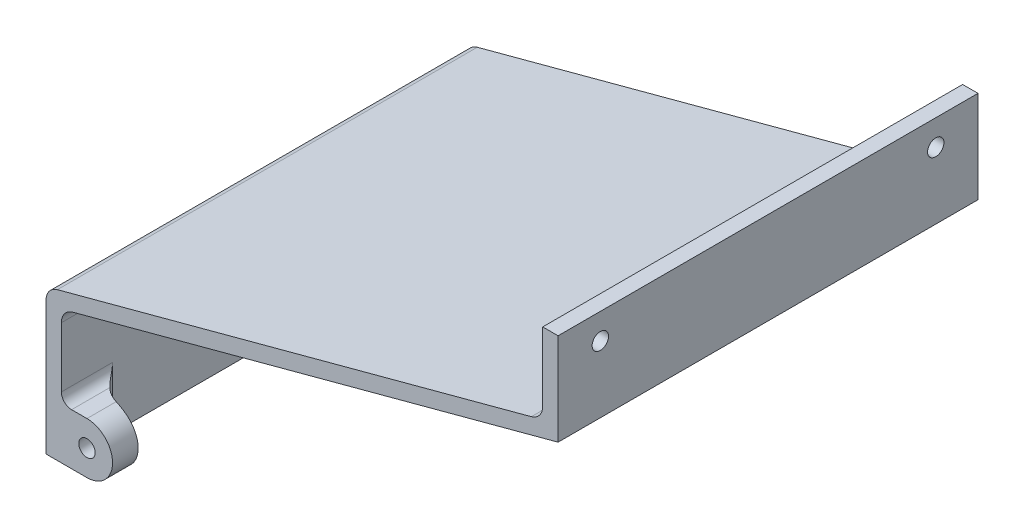
SolidWorks part; units mm, degrees
material "ABS"
ref_plane "前视基准面" through (0, 0, 0) normal (0, 0, 1) x (1, 0, 0)
ref_plane "上视基准面" through (0, 0, 0) normal (0, 1, 0) x (1, 0, 0)
ref_plane "右视基准面" through (0, 0, 0) normal (1, 0, 0) x (0, 0, -1)
sketch "草图1" plane through (0, 0, 0) normal (0, 0, 1) x (1, 0, 0)
  line L0 (49.6812, 34.5218) -> (49.6812, 16.5218)
  line L1 (49.6812, 16.5218) -> (-47.3188, -9.4692)
  line L2 (49.6812, 34.5218) -> (46.6812, 34.5218)
  line L3 (-47.3188, -9.4692) -> (-47.3188, -35.4782)
  line L4 (-50.3188, -7.1672) -> (-50.3188, -35.4782)
  line L5 (-47.3188, -35.4782) -> (-50.3188, -35.4782)
  line L6 (46.6812, 18.8238) -> (-50.3188, -7.1672)
  line L7 (46.6812, 34.5218) -> (46.6812, 18.8238)
extrude "凸台-拉伸2" add sketch "草图1" along normal blind 82
fillet "圆角1" radius 3 3 edges at (-50.3188, -7.1672, 41) (-47.3188, -9.4692, 41) (46.6812, 18.8238, 41)
sketch "草图2" plane through (0, 0, 0) normal (0, 0, -1) x (-1, 0, 0)
  line L0 (47.3188, -35.4782) -> (47.3188, -25.4782)
  line L1 (47.3188, -35.4782) -> (47.3188, -11.7712) construction
  line L2 (47.3188, -25.4782) -> (42.3188, -25.4782)
  line L4 (42.3188, -35.4782) -> (47.3188, -35.4782)
  arc A0 (42.3188, -25.4782) -> (42.3188, -35.4782) centre (42.3188, -30.4782) ccw
  circle A1 centre (42.3188, -30.4782) radius 1.6
  dimension "D2" = 5
  dimension "D3" = 3.2
  dimension "D1" = 5
extrude "凸台-拉伸3" add sketch "草图2" against normal blind 10
sketch "草图3" plane through (0, -35.4782, 0) normal (0, -1, 0) x (1, 0, 0)
  line L0 (-37.3188, 0) -> (-37.3188, 5) construction
  line L2 (-47.3188, 10) -> (-45.14, 6.5849) construction
  line L3 (-45.14, 6.5849) -> (-43.1087, 5.1416) construction
  line L4 (-43.1087, 5.1416) -> (-37.3188, 5) construction
  line L6 (-47.3188, 10) -> (-34.449, 10)
  line L7 (-34.449, 10) -> (-34.449, 5)
  line L8 (-34.449, 5) -> (-37.3188, 5)
  spline S0 degree 3 poles (-47.3188, 10) (-45.14, 6.5849) (-43.1087, 5.1416) (-37.3188, 5) knots 0 0 0 0 1 1 1 1
  dimension "D1" = 5
extrude "切除-拉伸1" cut sketch "草图3" against normal blind 10
sketch3d "3D草图1" plane through (0, 0, 0) normal (0, 0, 1) x (1, 0, 0)
  dimension "D1" = 5
sketch "草图6" plane through (49.6812, 0, 0) normal (1, 0, 0) x (0, 0, -1)
  line L0 (-82, 16.5218) -> (-82, 34.5218) construction
  line L1 (-82, 34.5218) -> (0, 34.5218) construction
  line L2 (-41, 34.5218) -> (-41, 28.1596) construction
  circle A0 centre (-73.75, 29.5218) radius 1.6
  circle A1 centre (-8.25, 29.5218) radius 1.6
  dimension "D3" = 3.2
  dimension "D1" = 8.25
  dimension "D2" = 5
extrude "后挡板前固定孔" cut sketch "草图6" against normal blind 10
sketch "草图7" plane through (0, 0, 82) normal (0, 0, 1) x (1, 0, 0)
  line L0 (-47.3188, -35.4782) -> (-42.3188, -35.4782)
  line L2 (-42.3188, -25.4782) -> (-47.3188, -25.4782)
  line L3 (-47.3188, -35.4782) -> (-47.3188, -11.7712) construction
  line L4 (-47.3188, -25.4782) -> (-47.3188, -35.4782)
  arc A0 (-42.3188, -35.4782) -> (-42.3188, -25.4782) centre (-42.3188, -30.4782) ccw
  circle A1 centre (-42.3188, -30.4782) radius 1.6
extrude "凸台-拉伸4" add sketch "草图7" against normal blind 10
sketch "草图8" plane through (0, -35.4782, 0) normal (0, -1, 0) x (1, 0, 0)
  line L0 (-37.3188, 82) -> (-37.3188, 77) construction
  line L1 (-37.3188, 72) -> (-37.3188, 82) construction
  line L5 (-47.3188, 72) -> (-44.9025, 75.7982) construction
  line L6 (-44.9025, 75.7982) -> (-42.8782, 76.7531) construction
  line L8 (-42.8782, 76.7531) -> (-37.3188, 77) construction
  line L9 (-47.3188, 72) -> (-36.003, 72)
  line L10 (-36.003, 72) -> (-36.003, 77)
  line L11 (-36.003, 77) -> (-37.3188, 77)
  spline S0 degree 3 poles (-47.3188, 72) (-44.9025, 75.7982) (-42.8782, 76.7531) (-37.3188, 77) knots 0 0 0 0 1 1 1 1
extrude "切除-拉伸2" cut sketch "草图8" against normal blind 10
fillet "圆角2" radius 2 2 edges at (-47.3188, -25.4782, 5) (-47.3188, -25.4782, 77)
sketch "草图4" plane through (0, 0, 5) normal (0, 0, -1) x (-1, 0, 0)
  circle A0 centre (42.3188, -30.4782) radius 3
  dimension "D1" = 6
extrude "后挡板后固定孔" cut sketch "草图4" against normal blind 10
sketch3d "3D草图2" plane through (0, 0, 0) normal (0, 0, 1) x (1, 0, 0)
  dimension "D1" = 5
sketch "草图9" plane through (0, 0, 77) normal (0, 0, 1) x (1, 0, 0)
  circle A0 centre (-42.3188, -30.4782) radius 3
  dimension "D1" = 6
extrude "切除-拉伸3" cut sketch "草图9" against normal blind 10
